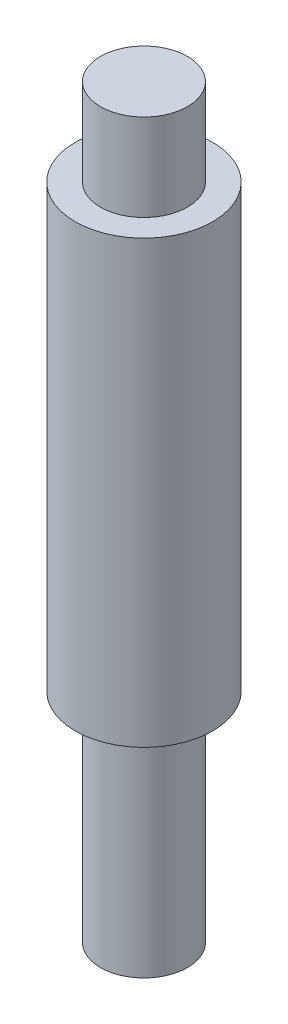
SolidWorks part; units mm, degrees
ref_plane "Front Plane" through (0, 0, 0) normal (0, 0, 1) x (1, 0, 0)
ref_plane "Top Plane" through (0, 0, 0) normal (0, 1, 0) x (1, 0, 0)
ref_plane "Right Plane" through (0, 0, 0) normal (1, 0, 0) x (0, 0, -1)
sketch "Sketch1" plane through (0, 0, 0) normal (0, 1, 0) x (1, 0, 0)
  circle A0 centre (0, 0) radius 6.35
  dimension "D1" = 12.7
extrude "BushingSprocketSpace" add sketch "Sketch1" along normal blind 31.75
sketch "Sketch2" plane through (0, 31.75, 0) normal (0, 1, 0) x (1, 0, 0)
  circle A0 centre (0, 0) radius 10.033
  dimension "D1" = 20.066
extrude "Boss-Extrude2" add sketch "Sketch2" along normal blind 64.3509
sketch "Sketch3" plane through (0, 96.1009, 0) normal (0, 1, 0) x (1, 0, 0)
  circle A0 centre (0, 0) radius 6.35
  dimension "D1" = 12.7
extrude "Boss-Extrude3" add sketch "Sketch3" along normal blind 12.7
